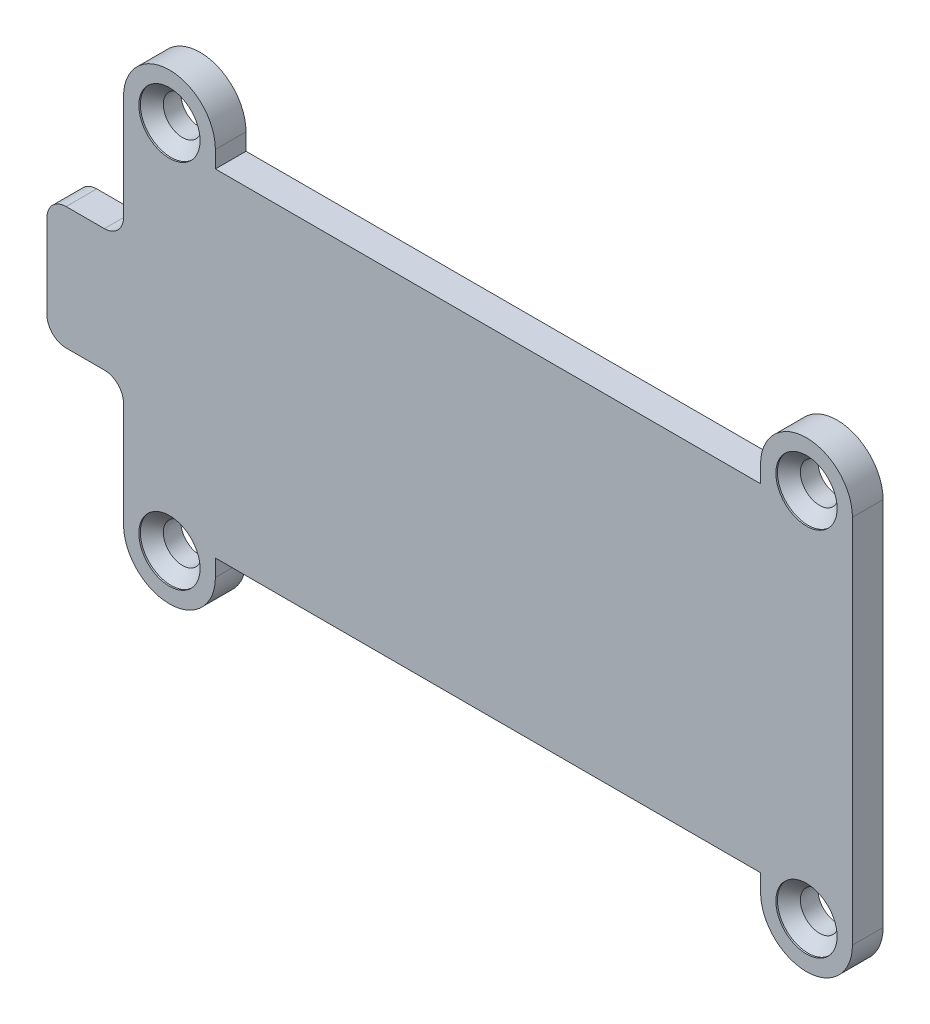
SolidWorks part; units mm, degrees
ref_plane "Front Plane" through (0, 0, 0) normal (0, 0, 1) x (1, 0, 0)
ref_plane "Top Plane" through (0, 0, 0) normal (0, 1, 0) x (1, 0, 0)
ref_plane "Right Plane" through (0, 0, 0) normal (1, 0, 0) x (0, 0, -1)
sketch "Sketch1" plane through (0, 0, 0) normal (0, 0, 1) x (1, 0, 0)
  line L3 (-28.8, 2.25) -> (-28.8, -2.25)
  line L4 (23.8, 12.1) -> (23.8, -12.1)
  line L52 (-25.05, 4) -> (-27.55, 4)
  line L53 (-28.8, 2.75) -> (-28.8, 2.25)
  line L54 (-28.8, 2.25) -> (-21.9, 2.25)
  line L55 (-21.9, 2.25) -> (-21.9, 9.1)
  line L56 (-21.9, 9.1) -> (21.9, 9.1)
  line L57 (21.9, 9.1) -> (21.9, 3.8)
  line L58 (21.9, 3.8) -> (23.8, 3.8)
  line L59 (23.8, 3.8) -> (23.8, 12.1)
  line L60 (17.8, 12.1) -> (17.8, 11)
  line L61 (17.8, 11) -> (-17.8, 11)
  line L62 (-17.8, 11) -> (-17.8, 12.1)
  line L63 (-23.8, 12.1) -> (-23.8, 5.25)
  line L64 (-25.05, 4) -> (-27.55, 4)
  line L65 (-28.8, 2.75) -> (-28.8, 2.25)
  line L72 (17.8, 12.1) -> (17.8, 11)
  line L73 (17.8, 11) -> (-17.8, 11)
  line L74 (-17.8, 11) -> (-17.8, 12.1)
  line L75 (-23.8, 12.1) -> (-23.8, 5.25)
  line L76 (-28.8, -2.25) -> (-28.8, -2.75)
  line L77 (-27.55, -4) -> (-25.05, -4)
  line L78 (-23.8, -5.25) -> (-23.8, -12.1)
  line L79 (-17.8, -12.1) -> (-17.8, -11)
  line L80 (-17.8, -11) -> (17.8, -11)
  line L81 (17.8, -11) -> (17.8, -12.1)
  line L82 (23.8, -12.1) -> (23.8, -3.8)
  line L83 (23.8, -3.8) -> (21.9, -3.8)
  line L84 (21.9, -3.8) -> (21.9, -9.1)
  line L85 (21.9, -9.1) -> (-21.9, -9.1)
  line L86 (-21.9, -9.1) -> (-21.9, -2.25)
  line L87 (-21.9, -2.25) -> (-28.8, -2.25)
  line L88 (-28.8, -2.25) -> (-28.8, -2.75)
  line L89 (-27.55, -4) -> (-25.05, -4)
  line L90 (-23.8, -5.25) -> (-23.8, -12.1)
  line L91 (-17.8, -12.1) -> (-17.8, -11)
  line L92 (-17.8, -11) -> (17.8, -11)
  line L93 (17.8, -11) -> (17.8, -12.1)
  circle A20 centre (-20.8, 12.1) radius 1.25
  circle A21 centre (20.8, 12.1) radius 1.25
  circle A22 centre (20.8, -12.1) radius 1.25
  circle A23 centre (-20.8, -12.1) radius 1.25
  arc A24 (-27.55, 4) -> (-28.8, 2.75) centre (-27.55, 2.75) ccw
  arc A25 (23.8, 12.1) -> (17.8, 12.1) centre (20.8, 12.1) ccw
  arc A26 (-17.8, 12.1) -> (-23.8, 12.1) centre (-20.8, 12.1) ccw
  arc A27 (-25.05, 4) -> (-23.8, 5.25) centre (-25.05, 5.25) ccw
  arc A28 (-27.55, 4) -> (-28.8, 2.75) centre (-27.55, 2.75) ccw
  arc A29 (23.8, 12.1) -> (17.8, 12.1) centre (20.8, 12.1) ccw
  arc A30 (-17.8, 12.1) -> (-23.8, 12.1) centre (-20.8, 12.1) ccw
  arc A31 (-25.05, 4) -> (-23.8, 5.25) centre (-25.05, 5.25) ccw
  arc A32 (-28.8, -2.75) -> (-27.55, -4) centre (-27.55, -2.75) ccw
  arc A33 (-23.8, -5.25) -> (-25.05, -4) centre (-25.05, -5.25) ccw
  arc A34 (-23.8, -12.1) -> (-17.8, -12.1) centre (-20.8, -12.1) ccw
  arc A35 (17.8, -12.1) -> (23.8, -12.1) centre (20.8, -12.1) ccw
  arc A36 (-28.8, -2.75) -> (-27.55, -4) centre (-27.55, -2.75) ccw
  arc A37 (-23.8, -5.25) -> (-25.05, -4) centre (-25.05, -5.25) ccw
  arc A38 (-23.8, -12.1) -> (-17.8, -12.1) centre (-20.8, -12.1) ccw
  arc A39 (17.8, -12.1) -> (23.8, -12.1) centre (20.8, -12.1) ccw
  dimension "D1" = 0
  dimension "D3" = 2.5
  dimension "D2" = 0
extrude "Boss-Extrude1" add sketch "Sketch1" along normal blind 2
hole_wizard "CSK for M2 Flat Head Machine Screw1" positions "Sketch2" profile "Sketch3" countersink size "M2" standard "ANSI Metric"
sketch "Sketch2" plane through (0, 0, 2) normal (0, 0, 1) x (1, 0, 0)
  point P0 (-20.8, 12.1)
  point P3 (20.8, 12.1)
  point P6 (20.8, -12.1)
  point P9 (-20.8, -12.1)
sketch "Sketch3" plane through (-20.8, 12.1, 2) normal (1, 0, 0) x (0, -1, 0)
  line L0 (0, 0) -> (0, 4.4009)
  line L1 (0, 4.4009) -> (1, 3.8)
  line L2 (1, 3.8) -> (1, 1.1)
  line L3 (1, 1.1) -> (2, 0.1)
  line L4 (2, 0.1) -> (2, 0)
  line L6 (2, 0) -> (0, 0)
  line L7 (-1, 1.1) -> (-2, 0.1) construction
  line L10 (0, 4.4009) -> (-1, 3.8) construction
  line L11 (0, -6.35) -> (0, 107.95) construction
  dimension "Hole Dia." = 2
  dimension "Hole Depth" = 3.8
  dimension "C'Sink Dia." = 4
  dimension "C'Sink Angle" = 90
  dimension "Drill Angle" = 118
  dimension "Head Clearance" = 0.1
